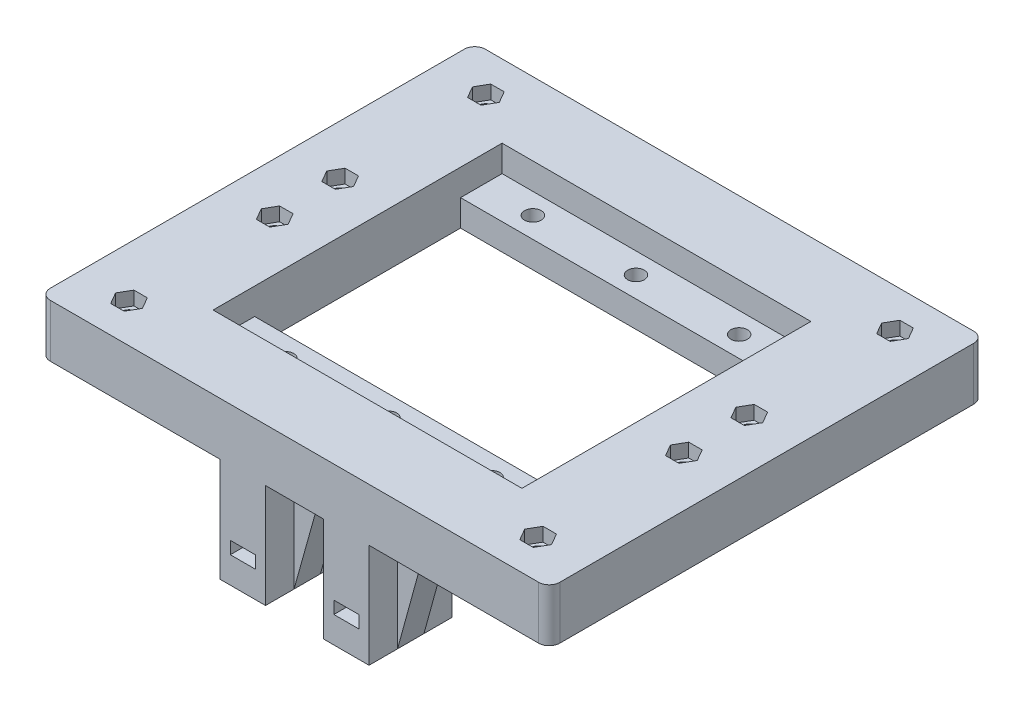
SolidWorks part; units mm, degrees
note: The reader was unsure of these and kept them because the rebuilt part matched: shared geometry of "Sketch2<4>", "Sketch10<3>", "Sketch5<2>", "Sketch6<2>".
ref_plane "Front Plane" through (0, 0, 0) normal (0, 0, 1) x (1, 0, 0)
ref_plane "Top Plane" through (0, 0, 0) normal (0, 1, 0) x (1, 0, 0)
ref_plane "Right Plane" through (0, 0, 0) normal (1, 0, 0) x (0, 0, -1)
sketch "Sketch2" plane through (0, 0, 0) normal (0, 1, 0) x (1, 0, 0)
  line L0 (110.49, 95.25) -> (110.49, 60.198) construction
  line L1 (0, 0) -> (122.555, 0)
  line L2 (0, 0) -> (0, 104.648)
  line L3 (0, 104.648) -> (122.555, 104.648)
  line L4 (122.555, 0) -> (122.555, 104.648)
  line L5 (24.13, 27.559) -> (98.425, 27.559)
  line L6 (24.13, 27.559) -> (24.13, 77.089)
  line L7 (24.13, 77.089) -> (98.425, 77.089)
  line L8 (98.425, 27.559) -> (98.425, 77.089)
  line L9 (24.13, 87.089) -> (98.425, 87.089)
  line L10 (24.13, 87.089) -> (24.13, 17.559)
  line L11 (24.13, 17.559) -> (98.425, 17.559)
  line L12 (98.425, 87.089) -> (98.425, 17.559)
  line L13 (110.49, 44.45) -> (110.49, 9.398) construction
  line L14 (73.7447, 22.86) -> (73.7447, 5.08) construction
  line L15 (86.1483, 22.559) -> (61.341, 22.559) construction
  line L16 (61.341, 22.559) -> (61.2775, 0) construction
  circle A0 centre (12.065, 95.25) radius 2
  circle A1 centre (12.065, 60.198) radius 2
  circle A2 centre (12.065, 44.45) radius 2
  circle A3 centre (12.065, 9.398) radius 2
  circle A4 centre (110.49, 9.398) radius 2
  circle A5 centre (110.49, 44.45) radius 2
  circle A6 centre (110.49, 60.198) radius 2
  circle A7 centre (110.49, 95.25) radius 2
  circle A8 centre (36.5337, 82.089) radius 2
  circle A9 centre (61.341, 82.089) radius 2
  circle A10 centre (86.1483, 82.089) radius 2
  circle A11 centre (86.1483, 22.559) radius 2
  circle A12 centre (61.341, 22.559) radius 2
  circle A13 centre (36.5337, 22.559) radius 2
  circle A14 centre (73.7447, 5.08) radius 2
  circle A15 centre (73.7447, 22.86) radius 2
  circle A16 centre (48.9392, 22.9298) radius 2
  circle A17 centre (48.8391, 5.1501) radius 2
  point P41 (110.49, 26.924)
  point P46 (73.7447, 13.97)
  point P47 (73.7447, 22.559)
  dimension "D11" = 4
  dimension "D12" = 4
  dimension "D20" = 35.052
  dimension "D24" = 4
  dimension "D1" = 104.648
  dimension "D2" = 122.555
  dimension "D3" = 17.78
  dimension "D4" = 12.954
  dimension "D5" = 27.559
  dimension "D6" = 27.559
  dimension "D7" = 10
  dimension "D8" = 10
  dimension "D9" = 24.13
  dimension "D10" = 24.13
  dimension "D13" = 12.065
  dimension "D14" = 12.065
  dimension "D15" = 12.4037
  dimension "D16" = 24.8073
  dimension "D17" = 24.8073
  dimension "D18" = 5
  dimension "D19" = 5
  dimension "D21" = 35.052
  dimension "D22" = 9.398
  dimension "D23" = 9.398
extrude "Boss-Extrude5" add sketch "Sketch2" along normal blind 12.7 contours L1 L4 L3 L2 L9 L12 L11 L10
extrude "Boss-Extrude7" add sketch "Sketch2<4>" along normal blind 6.35 contours L12 L9 L10 L7 A10 A9 A8 | L12 L5 L10 L11 A13 A12 A11
sketch "Sketch2<4>" plane through (0, 0, 0) normal (0, 1, 0) x (1, 0, 0) same geometry as "Sketch2"
sketch "Sketch3" plane through (0, 0, 0) normal (0, -1, 0) x (1, 0, 0)
  line L1 (13.6781, -6.604) -> (10.4519, -6.604)
  line L2 (10.4519, -6.604) -> (8.8388, -9.398)
  line L3 (8.8388, -9.398) -> (10.4519, -12.192)
  line L4 (10.4519, -12.192) -> (13.6781, -12.192)
  line L5 (13.6781, -12.192) -> (15.2912, -9.398)
  line L6 (15.2912, -9.398) -> (13.6781, -6.604)
  line L7 (13.6781, -92.456) -> (10.4519, -92.456)
  line L8 (10.4519, -92.456) -> (8.8388, -95.25)
  line L9 (8.8388, -95.25) -> (10.4519, -98.044)
  line L10 (10.4519, -98.044) -> (13.6781, -98.044)
  line L11 (13.6781, -98.044) -> (15.2912, -95.25)
  line L12 (15.2912, -95.25) -> (13.6781, -92.456)
  line L13 (112.1031, -92.456) -> (108.8769, -92.456)
  line L14 (108.8769, -92.456) -> (107.2638, -95.25)
  line L15 (107.2638, -95.25) -> (108.8769, -98.044)
  line L16 (108.8769, -98.044) -> (112.1031, -98.044)
  line L17 (112.1031, -98.044) -> (113.7162, -95.25)
  line L18 (113.7162, -95.25) -> (112.1031, -92.456)
  line L19 (108.8769, -12.192) -> (112.1031, -12.192)
  line L20 (112.1031, -12.192) -> (113.7162, -9.398)
  line L21 (113.7162, -9.398) -> (112.1031, -6.604)
  line L22 (112.1031, -6.604) -> (108.8769, -6.604)
  line L23 (108.8769, -6.604) -> (107.2638, -9.398)
  line L24 (107.2638, -9.398) -> (108.8769, -12.192)
  line L25 (13.6781, -62.992) -> (15.2912, -60.198)
  line L26 (15.2912, -60.198) -> (13.6781, -57.404)
  line L27 (13.6781, -57.404) -> (10.4519, -57.404)
  line L28 (10.4519, -57.404) -> (8.8388, -60.198)
  line L29 (8.8388, -60.198) -> (10.4519, -62.992)
  line L30 (10.4519, -62.992) -> (13.6781, -62.992)
  line L31 (8.8388, -44.45) -> (10.4519, -47.244)
  line L32 (10.4519, -47.244) -> (13.6781, -47.244)
  line L33 (13.6781, -47.244) -> (15.2912, -44.45)
  line L34 (15.2912, -44.45) -> (13.6781, -41.656)
  line L35 (13.6781, -41.656) -> (10.4519, -41.656)
  line L36 (10.4519, -41.656) -> (8.8388, -44.45)
  line L37 (107.2638, -44.45) -> (108.8769, -47.244)
  line L38 (108.8769, -47.244) -> (112.1031, -47.244)
  line L39 (112.1031, -47.244) -> (113.7162, -44.45)
  line L40 (113.7162, -44.45) -> (112.1031, -41.656)
  line L41 (112.1031, -41.656) -> (108.8769, -41.656)
  line L42 (108.8769, -41.656) -> (107.2638, -44.45)
  line L43 (108.8769, -57.404) -> (107.2638, -60.198)
  line L44 (107.2638, -60.198) -> (108.8769, -62.992)
  line L45 (108.8769, -62.992) -> (112.1031, -62.992)
  line L46 (112.1031, -62.992) -> (113.7162, -60.198)
  line L47 (113.7162, -60.198) -> (112.1031, -57.404)
  line L48 (112.1031, -57.404) -> (108.8769, -57.404)
  circle A0 centre (12.065, -9.398) radius 2.794 construction
  circle A1 centre (12.065, -9.398) radius 2 construction
  circle A2 centre (12.065, -9.398) radius 2
  circle A3 centre (12.065, -95.25) radius 2.794 construction
  circle A4 centre (110.49, -95.25) radius 2.794 construction
  circle A5 centre (110.49, -9.398) radius 2.794 construction
  circle A6 centre (110.49, -9.398) radius 2 construction
  circle A7 centre (110.49, -95.25) radius 2 construction
  circle A8 centre (12.065, -95.25) radius 2 construction
  circle A9 centre (110.49, -9.398) radius 2
  circle A10 centre (110.49, -95.25) radius 2
  circle A11 centre (12.065, -95.25) radius 2
  circle A12 centre (12.065, -60.198) radius 2 construction
  circle A13 centre (12.065, -44.45) radius 2 construction
  circle A14 centre (110.49, -44.45) radius 2 construction
  circle A15 centre (110.49, -60.198) radius 2 construction
  circle A16 centre (12.065, -60.198) radius 2
  circle A17 centre (12.065, -44.45) radius 2
  circle A18 centre (110.49, -44.45) radius 2
  circle A19 centre (110.49, -60.198) radius 2
  circle A20 centre (12.065, -60.198) radius 2.794 construction
  circle A21 centre (12.065, -44.45) radius 2.794 construction
  circle A22 centre (110.49, -44.45) radius 2.794 construction
  circle A23 centre (110.49, -60.198) radius 2.794 construction
  dimension "D1" = 5.588
extrude "Cut-Extrude1" cut sketch "Sketch3" along normal blind 3.302 from surface at -12.7 starting at face at (61.2775, 12.7, -52.324)
fillet "Fillet1" radius 2.54 4 edges at (122.555, 6.35, 0) (122.555, 6.35, -104.648) (0, 6.35, -104.648) (0, 6.35, 0)
sketch "Sketch4" plane through (0, 6.35, 0) normal (0, 1, 0) x (1, 0, 0)
  line L1 (39.7599, 22.559) -> (38.1468, 25.353)
  line L2 (38.1468, 25.353) -> (34.9206, 25.353)
  line L3 (34.9206, 25.353) -> (33.3074, 22.559)
  line L4 (33.3074, 22.559) -> (34.9206, 19.765)
  line L5 (34.9206, 19.765) -> (38.1468, 19.765)
  line L6 (38.1468, 19.765) -> (39.7599, 22.559)
  line L7 (58.1148, 22.559) -> (59.7279, 19.765)
  line L8 (59.7279, 19.765) -> (62.9541, 19.765)
  line L9 (62.9541, 19.765) -> (64.5672, 22.559)
  line L10 (64.5672, 22.559) -> (62.9541, 25.353)
  line L11 (62.9541, 25.353) -> (59.7279, 25.353)
  line L12 (59.7279, 25.353) -> (58.1148, 22.559)
  line L13 (82.9221, 22.559) -> (84.5352, 19.765)
  line L14 (84.5352, 19.765) -> (87.7614, 19.765)
  line L15 (87.7614, 19.765) -> (89.3746, 22.559)
  line L16 (89.3746, 22.559) -> (87.7614, 25.353)
  line L17 (87.7614, 25.353) -> (84.5352, 25.353)
  line L18 (84.5352, 25.353) -> (82.9221, 22.559)
  line L19 (82.9221, 82.089) -> (84.5352, 79.295)
  line L20 (84.5352, 79.295) -> (87.7614, 79.295)
  line L21 (87.7614, 79.295) -> (89.3746, 82.089)
  line L22 (89.3746, 82.089) -> (87.7614, 84.883)
  line L23 (87.7614, 84.883) -> (84.5352, 84.883)
  line L24 (84.5352, 84.883) -> (82.9221, 82.089)
  line L25 (64.5672, 82.089) -> (62.9541, 84.883)
  line L26 (62.9541, 84.883) -> (59.7279, 84.883)
  line L27 (59.7279, 84.883) -> (58.1148, 82.089)
  line L28 (58.1148, 82.089) -> (59.7279, 79.295)
  line L29 (59.7279, 79.295) -> (62.9541, 79.295)
  line L30 (62.9541, 79.295) -> (64.5672, 82.089)
  line L31 (39.7599, 82.089) -> (38.1468, 84.883)
  line L32 (38.1468, 84.883) -> (34.9206, 84.883)
  line L33 (34.9206, 84.883) -> (33.3074, 82.089)
  line L34 (33.3074, 82.089) -> (34.9206, 79.295)
  line L35 (34.9206, 79.295) -> (38.1468, 79.295)
  line L36 (38.1468, 79.295) -> (39.7599, 82.089)
  circle A0 centre (36.5337, 22.559) radius 2 construction
  circle A1 centre (61.341, 22.559) radius 2 construction
  circle A2 centre (86.1483, 22.559) radius 2 construction
  circle A3 centre (86.1483, 82.089) radius 2 construction
  circle A4 centre (61.341, 82.089) radius 2 construction
  circle A5 centre (36.5337, 82.089) radius 2 construction
  circle A6 centre (36.5337, 22.559) radius 2
  circle A7 centre (61.341, 22.559) radius 2
  circle A8 centre (86.1483, 22.559) radius 2
  circle A9 centre (86.1483, 82.089) radius 2
  circle A10 centre (61.341, 82.089) radius 2
  circle A11 centre (36.5337, 82.089) radius 2
  circle A12 centre (36.5337, 22.559) radius 2.794 construction
  circle A13 centre (61.341, 22.559) radius 2.794 construction
  circle A14 centre (86.1483, 22.559) radius 2.794 construction
  circle A15 centre (86.1483, 82.089) radius 2.794 construction
  circle A16 centre (61.341, 82.089) radius 2.794 construction
  circle A17 centre (36.5337, 82.089) radius 2.794 construction
  dimension "D1" = 5.588
extrude "Cut-Extrude2" cut sketch "Sketch4" along normal blind 3.302 from surface at -6.35 starting at face at (61.2775, 0, -52.324)
sketch "Sketch5" plane through (0, 6.35, 0) normal (0, 1, 0) x (1, 0, 0)
  line L1 (76.9709, 22.86) -> (75.3578, 25.654)
  line L2 (75.3578, 25.654) -> (72.1316, 25.654)
  line L3 (72.1316, 25.654) -> (70.5184, 22.86)
  line L4 (70.5184, 22.86) -> (72.1316, 20.066)
  line L5 (72.1316, 20.066) -> (75.3578, 20.066)
  line L6 (75.3578, 20.066) -> (76.9709, 22.86)
  line L7 (52.1655, 22.9298) -> (50.5523, 25.7238)
  line L8 (50.5523, 25.7238) -> (47.3261, 25.7238)
  line L9 (47.3261, 25.7238) -> (45.713, 22.9298)
  line L10 (45.713, 22.9298) -> (47.3261, 20.1358)
  line L11 (47.3261, 20.1358) -> (50.5523, 20.1358)
  line L12 (50.5523, 20.1358) -> (52.1655, 22.9298)
  circle A0 centre (73.7447, 22.86) radius 2 construction
  circle A1 centre (48.9392, 22.9298) radius 2 construction
  circle A2 centre (73.7447, 22.86) radius 2
  circle A3 centre (48.9392, 22.9298) radius 2
  circle A4 centre (73.7447, 22.86) radius 2.794 construction
  circle A5 centre (48.9392, 22.9298) radius 2.794 construction
  circle A6 centre (48.8391, 5.1501) radius 2 construction
  circle A7 centre (73.7447, 5.08) radius 2 construction
  circle A8 centre (48.8391, 5.1501) radius 2
  circle A9 centre (73.7447, 5.08) radius 2
  circle M8 centre (73.7447, 22.86) radius 2
  circle M9 centre (48.9392, 22.9298) radius 2
  dimension "D1" = 5.588
extrude "Cut-Extrude3" cut sketch "Sketch5" against normal blind 3.302
sketch "Sketch6" plane through (0, 12.7, 0) normal (0, 1, 0) x (1, 0, 0)
  line L1 (70.5184, 5.08) -> (72.1316, 2.286)
  line L2 (72.1316, 2.286) -> (75.3578, 2.286)
  line L3 (75.3578, 2.286) -> (76.9709, 5.08)
  line L4 (76.9709, 5.08) -> (75.3578, 7.874)
  line L5 (75.3578, 7.874) -> (72.1316, 7.874)
  line L6 (72.1316, 7.874) -> (70.5184, 5.08)
  line L7 (45.6129, 5.1501) -> (47.226, 2.3561)
  line L8 (47.226, 2.3561) -> (50.4522, 2.3561)
  line L9 (50.4522, 2.3561) -> (52.0654, 5.1501)
  line L10 (52.0654, 5.1501) -> (50.4522, 7.9441)
  line L11 (50.4522, 7.9441) -> (47.226, 7.9441)
  line L12 (47.226, 7.9441) -> (45.6129, 5.1501)
  circle A0 centre (48.8391, 5.1501) radius 2 construction
  circle A1 centre (73.7447, 5.08) radius 2 construction
  circle A2 centre (48.8391, 5.1501) radius 2
  circle A3 centre (73.7447, 5.08) radius 2
  circle A4 centre (73.7447, 5.08) radius 2.794 construction
  circle A5 centre (48.8391, 5.1501) radius 2.794 construction
  dimension "D1" = 5.588
extrude "Cut-Extrude4" cut sketch "Sketch6" against normal blind 3.302
sketch "Sketch7" plane through (0, 0, 0) normal (0, -1, 0) x (1, 0, 0)
  line L0 (2.54, 0) -> (120.015, 0) construction
  line L1 (41.3391, 0) -> (56.3391, 0)
  line L2 (41.3391, 0) -> (41.3391, -27.559)
  line L3 (41.3391, -27.559) -> (56.3391, -27.559)
  line L4 (56.3391, 0) -> (56.3391, -27.559)
  line L5 (24.13, -27.559) -> (98.425, -27.559) construction
  line L6 (41.3391, -20) -> (56.3391, -20)
  line L7 (66.2447, 0) -> (81.2447, 0)
  line L8 (66.2447, 0) -> (66.2447, -27.559)
  line L9 (66.2447, -27.559) -> (81.2447, -27.559)
  line L10 (81.2447, 0) -> (81.2447, -27.559)
  line L11 (66.2447, -20) -> (81.2447, -20)
  line L12 (54.3071, 0) -> (54.3071, -20)
  line L13 (43.3711, -20) -> (43.3711, 0)
  line L14 (68.2767, -20) -> (68.2767, 0)
  line L15 (79.2127, -20) -> (79.2127, 0)
  circle A0 centre (48.8391, -5.1501) radius 2 construction
  circle A1 centre (73.7447, -5.08) radius 2 construction
  dimension "D1" = 7.5
  dimension "D2" = 15
  dimension "D3" = 15
  dimension "D4" = 7.5
  dimension "D5" = 20
  dimension "D6" = 2.032
  dimension "D7" = 2.032
  dimension "D8" = 2.032
  dimension "D9" = 2.032
extrude "Boss-Extrude8" add sketch "Sketch7" along normal blind 25 contours L2 L6 L4 L1 | L8 L11 L10 L7
sketch "Sketch8" plane through (0, -25, 0) normal (0, -1, 0) x (1, 0, 0)
  line L1 (51.6331, -6.7632) -> (51.6331, -3.537)
  line L2 (51.6331, -3.537) -> (48.8391, -1.9239)
  line L3 (48.8391, -1.9239) -> (46.0451, -3.537)
  line L4 (46.0451, -3.537) -> (46.0451, -6.7632)
  line L5 (46.0451, -6.7632) -> (48.8391, -8.3763)
  line L6 (48.8391, -8.3763) -> (51.6331, -6.7632)
  line L7 (76.5387, -6.6931) -> (76.5387, -3.4669)
  line L8 (76.5387, -3.4669) -> (73.7447, -1.8538)
  line L9 (73.7447, -1.8538) -> (70.9507, -3.4669)
  line L10 (70.9507, -3.4669) -> (70.9507, -6.6931)
  line L11 (70.9507, -6.6931) -> (73.7447, -8.3062)
  line L12 (73.7447, -8.3062) -> (76.5387, -6.6931)
  line L13 (51.6331, -16.9232) -> (51.6331, -13.697)
  line L14 (51.6331, -13.697) -> (48.8391, -12.0839)
  line L15 (48.8391, -12.0839) -> (46.0451, -13.697)
  line L16 (46.0451, -13.697) -> (46.0451, -16.9232)
  line L17 (46.0451, -16.9232) -> (48.8391, -18.5363)
  line L18 (48.8391, -18.5363) -> (51.6331, -16.9232)
  line L19 (76.5387, -16.9232) -> (76.5387, -13.697)
  line L20 (76.5387, -13.697) -> (73.7447, -12.0839)
  line L21 (73.7447, -12.0839) -> (70.9507, -13.697)
  line L22 (70.9507, -13.697) -> (70.9507, -16.9232)
  line L23 (70.9507, -16.9232) -> (73.7447, -18.5363)
  line L24 (73.7447, -18.5363) -> (76.5387, -16.9232)
  circle A0 centre (48.8391, -5.1501) radius 2 construction
  circle A1 centre (73.7447, -5.08) radius 2 construction
  circle A2 centre (48.8391, -5.1501) radius 2
  circle A3 centre (73.7447, -5.08) radius 2
  circle A4 centre (48.8391, -5.1501) radius 2.794 construction
  circle A5 centre (73.7447, -5.08) radius 2.794 construction
  circle A6 centre (48.8391, -15.3101) radius 2
  circle A7 centre (73.7447, -15.3101) radius 2
  circle A8 centre (48.8391, -15.3101) radius 2.794 construction
  circle A9 centre (73.7447, -15.3101) radius 2.794 construction
  dimension "D1" = 5.588
  dimension "D2" = 10.16
extrude "Cut-Extrude6" cut sketch "Sketch8" against normal blind 19.05 contours A6 | A2 | A3 | A7
sketch "Sketch9" plane through (0, 0, 0) normal (0, 0, 1) x (1, 0, 0)
  line L0 (2.54, 0) -> (43.3711, 0) construction
  line L1 (43.3711, -25) -> (43.3711, 0) construction
  line L2 (54.3071, -25) -> (54.3071, 0) construction
  line L3 (68.2767, -25) -> (68.2767, 0) construction
  line L4 (54.3071, 0) -> (68.2767, 0) construction
  line L5 (79.2127, -25) -> (79.2127, 0) construction
  line L6 (79.2127, 0) -> (120.015, 0) construction
  line L7 (36.5131, 0) -> (43.3711, 0)
  line L8 (43.3711, -25) -> (43.3711, 0)
  line L9 (54.3071, -25) -> (54.3071, 0)
  line L10 (68.2767, -25) -> (68.2767, 0)
  line L11 (54.3071, 0) -> (68.2767, 0)
  line L12 (79.2127, -25) -> (79.2127, 0)
  line L13 (79.2127, 0) -> (86.0707, 0)
  line L14 (43.3711, -25) -> (36.5131, 0)
  line L15 (54.3071, -25) -> (61.2919, 0)
  line L16 (68.2767, -25) -> (61.2919, 0)
  line L17 (79.2127, -25) -> (86.0707, 0)
  line M2 (2.54, 0) -> (43.3711, 0)
  line M3 (43.3711, 0) -> (43.3711, -25)
  line M5 (54.3071, -25) -> (54.3071, 0)
  line M6 (54.3071, 0) -> (68.2767, 0)
  line M7 (68.2767, 0) -> (68.2767, -25)
  line M9 (79.2127, -25) -> (79.2127, 0)
  line M10 (79.2127, 0) -> (120.015, 0)
  dimension "D1" = 6.858
  dimension "D2" = 6.858
extrude "Boss-Extrude9" add sketch "Sketch9" against normal mid plane 6.35 from offset 10.033 contours L16 L11 M7 | L17 M9 M10 | L15 M5 M6 | L14 M3 M2 offset against normal yes
sketch "Sketch10" plane through (0, 0, 0) normal (0, 0, 1) x (1, 0, 0)
  line L0 (50.8391, -25) -> (50.8391, -5.95) construction
  line L1 (46.8391, -5.95) -> (46.8391, -25) construction
  line L2 (71.7447, -5.95) -> (71.7447, -25) construction
  line L3 (75.7447, -25) -> (75.7447, -5.95) construction
  line L4 (50.8391, -25) -> (50.8391, -5.95) construction
  line L5 (46.8391, -5.95) -> (46.8391, -25) construction
  line L6 (71.7447, -5.95) -> (71.7447, -25) construction
  line L7 (75.7447, -25) -> (75.7447, -5.95) construction
  line L8 (46.8391, -5.95) -> (50.8391, -5.95) construction
  line L9 (45.8391, -15.65) -> (51.8391, -15.65)
  line L10 (45.8391, -15.65) -> (45.8391, -18.65)
  line L11 (45.8391, -18.65) -> (51.8391, -18.65)
  line L12 (51.8391, -15.65) -> (51.8391, -18.65)
  line L13 (70.7447, -15.65) -> (76.7447, -15.65)
  line L14 (70.7447, -15.65) -> (70.7447, -18.65)
  line L15 (70.7447, -18.65) -> (76.7447, -18.65)
  line L16 (76.7447, -15.65) -> (76.7447, -18.65)
  line L17 (71.7447, -5.95) -> (75.7447, -5.95) construction
  line L18 (43.3711, -25) -> (54.3071, -25) construction
  point P1 (73.7447, -15.65)
  point P18 (73.7447, -5.95)
  point P19 (48.8391, -15.65)
  point P20 (48.8391, -5.95)
  dimension "D1" = 6
  dimension "D2" = 3
  dimension "D3" = 6.35
extrude "Cut-Extrude7" cut sketch "Sketch10" against normal blind 8.382
extrude "Cut-Extrude15" cut sketch "Sketch10<3>" along normal blind 8.382 from offset 20 offset against normal yes
sketch "Sketch10<3>" plane through (0, 0, 0) normal (0, 0, 1) x (1, 0, 0) same geometry as "Sketch10"
extrude "Boss-Extrude10" add sketch "Sketch5<2>" against normal up to surface (6.35 mm away) contours L11 L12 L7 L8 L9 L10 M9 | M9 | L5 L6 L1 L2 L3 L4 M8 | M8 up to face at (61.341, 0, -82.089)
sketch "Sketch5<2>" plane through (0, 6.35, 0) normal (0, 1, 0) x (1, 0, 0) same geometry as "Sketch5"
extrude "Boss-Extrude11" add sketch "Sketch6<2>" against normal up to surface (12.7 mm away) contours A2 | L11 L12 L7 L8 L9 L10 A2 | L5 L6 L1 L2 L3 L4 A3 | A3 up to face at (48.8391, 0, -7.1501)
sketch "Sketch6<2>" plane through (0, 12.7, 0) normal (0, 1, 0) x (1, 0, 0) same geometry as "Sketch6"
